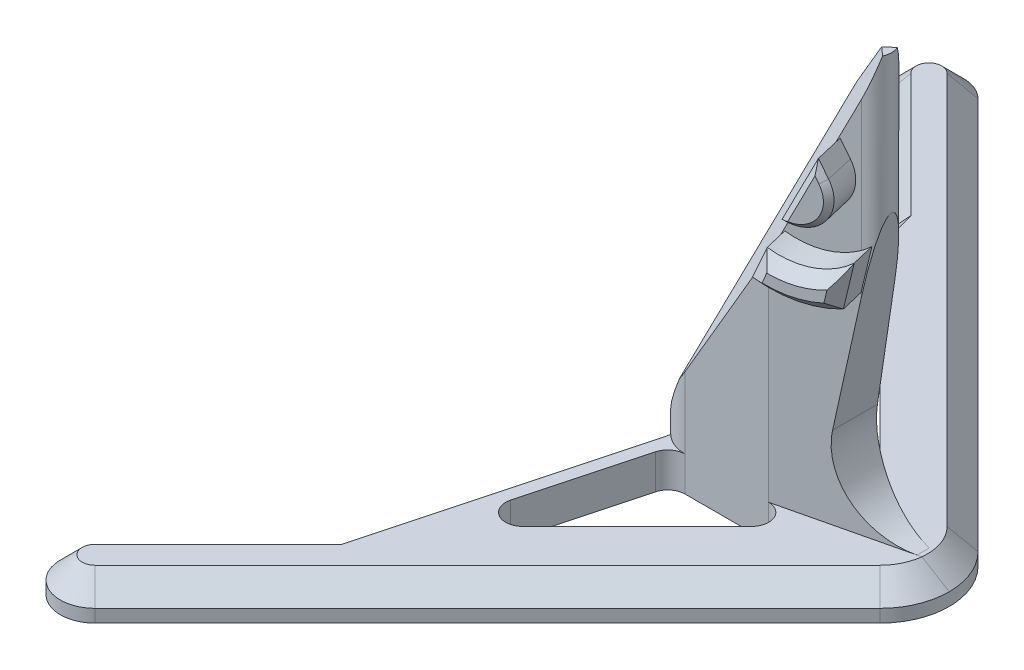
SolidWorks part; units mm, degrees
ref_plane "Front Plane" through (0, 0, 0) normal (0, 0, 1) x (1, 0, 0)
ref_plane "Top Plane" through (0, 0, 0) normal (0, 1, 0) x (1, 0, 0)
ref_plane "Right Plane" through (0, 0, 0) normal (1, 0, 0) x (0, 0, -1)
sketch "Sketch1" plane through (0, 0, 0) normal (0, 1, 0) x (1, 0, 0)
  line L0 (-3.175, 3.175) -> (-20.5235, 20.5235)
  line L1 (0, 0) -> (-76.2919, 0) construction
  line L2 (4.4901, 4.4901) -> (-31.4309, 40.4112)
  line L3 (4.4901, -4.4901) -> (-31.4309, -40.4112)
  line L4 (-3.175, -3.175) -> (-20.5235, -20.5235)
  line L5 (-3.175, 3.175) -> (-15.875, 3.175)
  line L6 (-3.175, -3.175) -> (-15.875, -3.175)
  line L7 (-15.875, -3.175) -> (-20.5235, -20.5235)
  line L8 (0, 0) -> (-35.921, 35.921) construction
  line L9 (-18.9418, -2.3532) -> (-23.5903, -19.7018)
  line L10 (-25.0137, -25.0137) -> (-35.921, -35.921)
  line L11 (-23.5903, -19.7018) -> (-25.0137, -25.0137)
  line L12 (-25.0137, 25.0137) -> (-35.921, 35.921)
  line L13 (-18.9418, 2.3532) -> (-23.5903, 19.7018)
  line L14 (-23.5903, 19.7018) -> (-25.0137, 25.0137)
  line L15 (-15.875, 3.175) -> (-20.5235, 20.5235)
  arc A0 (-35.921, 35.921) -> (-31.4309, 40.4112) centre (-33.676, 38.1661) cw
  arc A1 (-35.921, -35.921) -> (-31.4309, -40.4112) centre (-33.676, -38.1661) ccw
  arc A2 (4.4901, -4.4901) -> (4.4901, 4.4901) centre (0, 0) ccw
  arc A3 (-18.9418, -2.3532) -> (-18.9418, 2.3532) centre (-27.7243, 0) ccw
  dimension "D1" = 50.8
  dimension "D2" = 45
  dimension "D4" = 12.7
  dimension "D5" = 3.175
  dimension "D6" = 30
  dimension "D3" = 6.35
  dimension "D7" = 3.175
extrude "Boss-Extrude1" add sketch "Sketch1" along normal blind 3.175
fillet "Fillet2" radius 1.5875 6 edges at (-20.5235, 1.5875, 20.5235) (-15.875, 1.5875, 3.175) (-3.175, 1.5875, 3.175) (-3.175, 1.5875, -3.175) (-15.875, 1.5875, -3.175) (-20.5235, 1.5875, -20.5235)
sketch "Sketch2" plane through (0, 3.175, 0) normal (0, 1, 0) x (1, 0, 0)
  line L0 (-14.6569, 3.175) -> (-7.0076, 3.175) construction
  line L1 (-7.0076, -3.175) -> (-14.6569, -3.175) construction
  line L2 (-14.6569, 3.175) -> (-7.0076, 3.175)
  line L3 (-7.0076, -3.175) -> (-14.6569, -3.175)
  line L4 (-7.0076, -3.175) -> (6.35, 0)
  line L5 (6.35, 0) -> (-7.0076, 3.175)
  line L6 (-17.8319, 0) -> (6.35, 0) construction
  arc A1 (-14.6569, -3.175) -> (-16.1903, -4.3516) centre (-14.6569, -4.7625) ccw construction
  arc A2 (-16.1903, 4.3516) -> (-14.6569, 3.175) centre (-14.6569, 4.7625) ccw construction
  arc A12 (-14.6569, -3.175) -> (-14.6569, 3.175) centre (-14.6569, 0) cw
extrude "Boss-Extrude2" add sketch "Sketch2" along normal blind 38.1
ref_plane "Plane1" through (0, 0, 0) normal (0, 0, 1) x (1, 0, 0)
sketch "Sketch5" plane through (0, 0, 0) normal (0, 0, 1) x (1, 0, 0)
  line L0 (-17.8319, 41.275) -> (-17.8319, 3.175)
  line L1 (-17.8319, 3.175) -> (-0.3288, 41.275)
  line L2 (-7.0076, 41.275) -> (6.35, 41.275) construction
  line L3 (-0.3288, 41.275) -> (-17.8319, 41.275)
extrude "Cut-Extrude2" cut sketch "Sketch5" against normal through all both and the other way through all
chamfer "Chamfer1" distance 2 angle 45 2 edges at (-3.6682, 34.006, 2.3812) (-3.6682, 34.006, -2.3812) first distance on face at (-9.0191, 22.3584, 0)
chamfer "Chamfer2" distance 2 angle 45 11 edges at (5.8666, 3.175, -2.43) (5.8666, 3.175, 2.43) (-13.4704, 3.175, -22.4506) (-35.921, 3.175, -40.4112) (-30.4673, 3.175, -30.4673) (-21.9777, 3.175, -13.6835) (-18.632, 3.175, 0) (-21.9777, 3.175, 13.6835) (-30.4673, 3.175, 30.4673) (-35.921, 3.175, 40.4112) (-13.4704, 3.175, 22.4506)
fillet "Fillet3" radius 1.5875 1 edges at (6.35, 21.225, 0)
sketch "Sketch7" plane through (0, 0, 0) normal (0, 0, 1) x (1, 0, 0)
  line L0 (1.0726, 28.575) -> (-3.6899, 3.175)
  line L1 (1.0726, 3.175) -> (1.0726, 41.275) construction
  line L2 (-32.8451, 3.175) -> (3.0759, 3.175) construction
  line L3 (-3.6899, 3.175) -> (1.0726, 3.175)
  line L4 (1.0726, 3.175) -> (1.0726, 28.575)
  dimension "D1" = 4.7625
  dimension "D2" = 25.4
extrude "Cut-Extrude3" cut sketch "Sketch7" against normal through all both and the other way through all
fillet "Fillet4" radius 6.35 1 edges at (-3.6899, 3.175, 0)
sketch "Sketch8" plane through (0.3396, 0, 1.4286) normal (0.2313, 0, 0.9729) x (0.9729, 0, -0.2313)
  line L1 (-0.532, 22.4054) -> (0.2967, 26.3613)
  line L2 (-6.3232, 25.1481) -> (-7.4355, 22.3886)
  line L7 (-1.3421, 32.7046) -> (-2.1228, 34.0568)
  line L8 (-2.1228, 34.0568) -> (-4.8793, 28.219)
  arc A2 (-6.3232, 25.1481) -> (0.2967, 26.3613) centre (-4.0051, 31.1671) ccw
  arc A5 (-4.8793, 28.219) -> (-1.3421, 32.7046) centre (-4.0051, 31.1671) ccw
  arc A8 (-7.4355, 22.3886) -> (-0.532, 22.4054) centre (-4.0051, 31.1671) ccw
  point P0 (-4.0051, 31.1671)
  point P5 (-9.5044, 27.9921)
  point P6 (1.4941, 34.3421)
  point P10 (-4.0051, 31.1671)
  point P11 (-12.254, 26.4046)
  point P12 (4.2438, 35.9296)
extrude "Boss-Extrude3" add sketch "Sketch8" along normal blind 3.175
chamfer "Chamfer3" distance 1 angle 45 4 edges at (0.9593, 24.3833, 4.5448) (-2.8004, 21.7422, 5.4384) (-5.6191, 23.7683, 6.1084) (-1.6916, 24.8228, 5.1749)
chamfer "Chamfer4" distance 0.5 angle 45 3 edges at (-0.6117, 33.3807, 4.9182) (-0.4736, 29.2631, 4.8854) (-2.3324, 31.1379, 5.3272)
